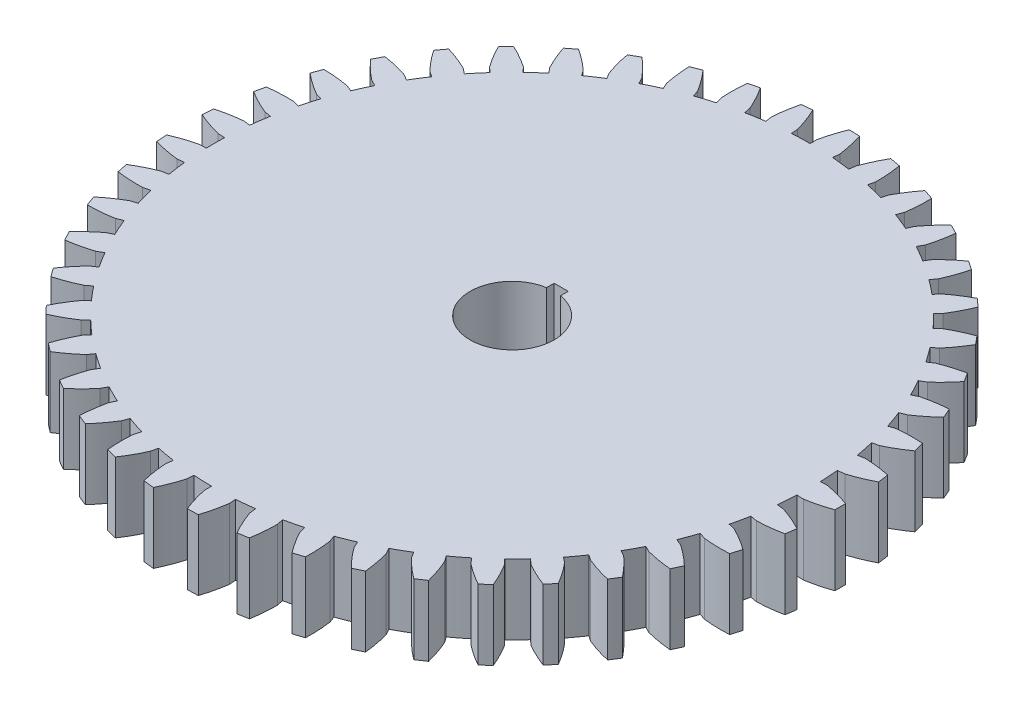
SolidWorks part; units mm, degrees
ref_plane "Front Plane" through (0, 0, 0) normal (0, 0, 1) x (1, 0, 0)
ref_plane "Top Plane" through (0, 0, 0) normal (0, 1, 0) x (1, 0, 0)
ref_plane "Right Plane" through (0, 0, 0) normal (1, 0, 0) x (0, 0, -1)
sketch "Sketch1" plane through (0, 0, 0) normal (0, 1, 0) x (1, 0, 0)
  circle A3 centre (0, 0) radius 21.25
  circle A4 centre (0, 0) radius 23.5
  circle A5 centre (0, 0) radius 22.5
  circle A6 centre (0, 0) radius 21.5
  circle A7 centre (0, 0) radius 21.7333
  dimension "pitch circle" = 45
  dimension "addendum circle" = 47
  dimension "root circle" = 42.5
  dimension "clearance circle" = 43
  dimension "base circle" = 43.4667
sketch "Sketch2" plane through (0, 0, 0) normal (0, 1, 0) x (1, 0, 0)
  line L0 (0, 0) -> (0, 21.7333)
  line L1 (0, 0) -> (10.8667, 18.8216) construction
  line L2 (0, 0) -> (18.8216, 10.8667) construction
  line L3 (0, 0) -> (21.7333, 0) construction
  line L4 (21.7333, 0) -> (21.7333, 34.1386) construction
  line L5 (18.8216, 10.8667) -> (7.4421, 30.5766) construction
  line L6 (10.8667, 18.8216) -> (1.0117, 24.5114) construction
  line L7 (0, 0) -> (3.1314, 22.281)
  line L8 (0, 0) -> (1.5695, 22.4452) construction
  line L9 (0.8822, 22.4827) -> (0, 0) construction
  circle A0 centre (0, 0) radius 21.7333 construction
  circle A1 centre (0, 0) radius 22.5 construction
  arc A2 (1.5695, 22.4452) -> (0.1941, 22.4992) centre (0, 0) ccw
  spline S0 degree 3 poles (0, 21.7333) (1.9118, 30.6335) (14.3992, 34.1502) (21.7333, 34.1386) knots 0 0 0 0 1 1 1 1
  spline S1 degree 3 poles (1.703, 21.6665) (0.4945, 30.6891) (-11.679, 35.1735) (-18.9914, 35.7367) knots 0 0 0 0 1 1 1 1
  point P11 (0, 0)
  dimension "Involute Control" = 90
  dimension "Base circle quarter circumference" = 34.1386
  dimension "D1" = 22.7591
  dimension "D2" = 11.3795
  dimension "pitch circle" = 8
  dimension "Involute array" = 4
sketch "Sketch3" plane through (0, 0, 0) normal (0, 1, 0) x (1, 0, 0)
  line L0 (1.703, 21.6665) -> (1.6651, 21.1847)
  line L1 (0, 0) -> (0, 21.7333) construction
  line L3 (0, 21.25) -> (0, 21.7333)
  arc A1 (0.5394, 23.4938) -> (0, 21.7333) centre (10.5142, 19.4749) ccw
  circle A2 centre (0, 0) radius 23.5 construction
  circle A3 centre (0, 0) radius 21.25 construction
  arc A7 (1.703, 21.6665) -> (1.3032, 23.4638) centre (-8.9558, 20.2389) ccw
  arc A8 (1.6651, 21.1847) -> (0, 21.25) centre (0, 0) ccw
  arc A9 (1.3032, 23.4638) -> (0.5394, 23.4938) centre (0, 0) ccw
  circle A10 centre (0, 0) radius 21.7333 construction
  spline S0 degree 3 poles (1.703, 21.6665) (0.4945, 30.6891) (-11.679, 35.1735) (-18.9914, 35.7367) knots 0 0 0 0 1 1 1 1 construction
  spline S1 degree 3 poles (0, 21.7333) (1.9118, 30.6335) (14.3992, 34.1502) (21.7333, 34.1386) knots 0 0 0 0 1 1 1 1 construction
extrude "Boss-Extrude1" add sketch "Sketch3" along normal blind 5
sketch "Sketch5" plane through (0, 0, 0) normal (1, 0, 0) x (0, 0, -1)
  line L0 (0, 0) -> (0, 5.4709) construction
pattern_circular "CirPattern4" count 45 over 360 about axis through (0, 0, 0) along (0, 1, 0) reverse direction yes of bodies 101
sketch "Sketch6" plane through (0, 0, 0) normal (0, 1, 0) x (1, 0, 0)
  circle A0 centre (0, 0) radius 21.25 construction
  circle A1 centre (0, 0) radius 21.25
extrude "Boss-Extrude2" add sketch "Sketch6" along normal up to surface (5 mm away) up to face at (20.2011, 5, 9.0987)
sketch "Sketch7" plane through (0, 5, 0) normal (0, 1, 0) x (1, 0, 0)
  line L1 (-0.5, 3.5) -> (0.5, 3.5)
  line L2 (-0.5, 3.5) -> (-0.5, 2.5)
  line L3 (-0.5, 2.5) -> (0.5, 2.5)
  line L4 (0.5, 3.5) -> (0.5, 2.5)
  line L5 (-0.5, 3.5) -> (0.5, 2.5) construction
  line L6 (-0.5, 2.5) -> (0.5, 3.5) construction
  circle A0 centre (0, 0) radius 3
  point P3 (0, 3)
  dimension "D1" = 6
  dimension "D2" = 1
extrude "Cut-Extrude1" cut sketch "Sketch7" against normal through all contours L2 A0 L4 L3 | L4 A0 L2 L3 | L4 L3 L2 L1 region at (0, 5, -2.7432) region at (0, 5, 0.048)
equation "\"Module\" = 1"
equation "\"Teeth number\" = 45"
equation "\"Pressure angle\" = 15"
equation "\"pitch circle@Sketch1\"= \"Module\" * \"Teeth number\""
equation "\"addendum circle@Sketch1\"= \"pitch circle@Sketch1\" + ( \"Module\" * 2 )"
equation "\"root circle@Sketch1\"= \"pitch circle@Sketch1\" - ( ( \"Module\" * 1.25 ) * 2 )"
equation "\"clearance circle@Sketch1\"= \"pitch circle@Sketch1\" - ( \"Module\" * 2 )"
equation "\"base circle@Sketch1\"= \"pitch circle@Sketch1\" * cos ( \"Pressure angle\" )"
equation "\"D1@Sketch2\"=\"Base circle quarter circumference@Sketch2\"/3*2"
equation "\"D2@Sketch2\"=\"Base circle quarter circumference@Sketch2\"/3"
equation "\"pitch circle@Sketch2\"=360/\"Teeth number\""
equation "\"D1@CirPattern4\"=\"Teeth number\""
equation "\"Base circle quarter circumference@Sketch2\"= \"base circle@Sketch1\" * pi / 4"
